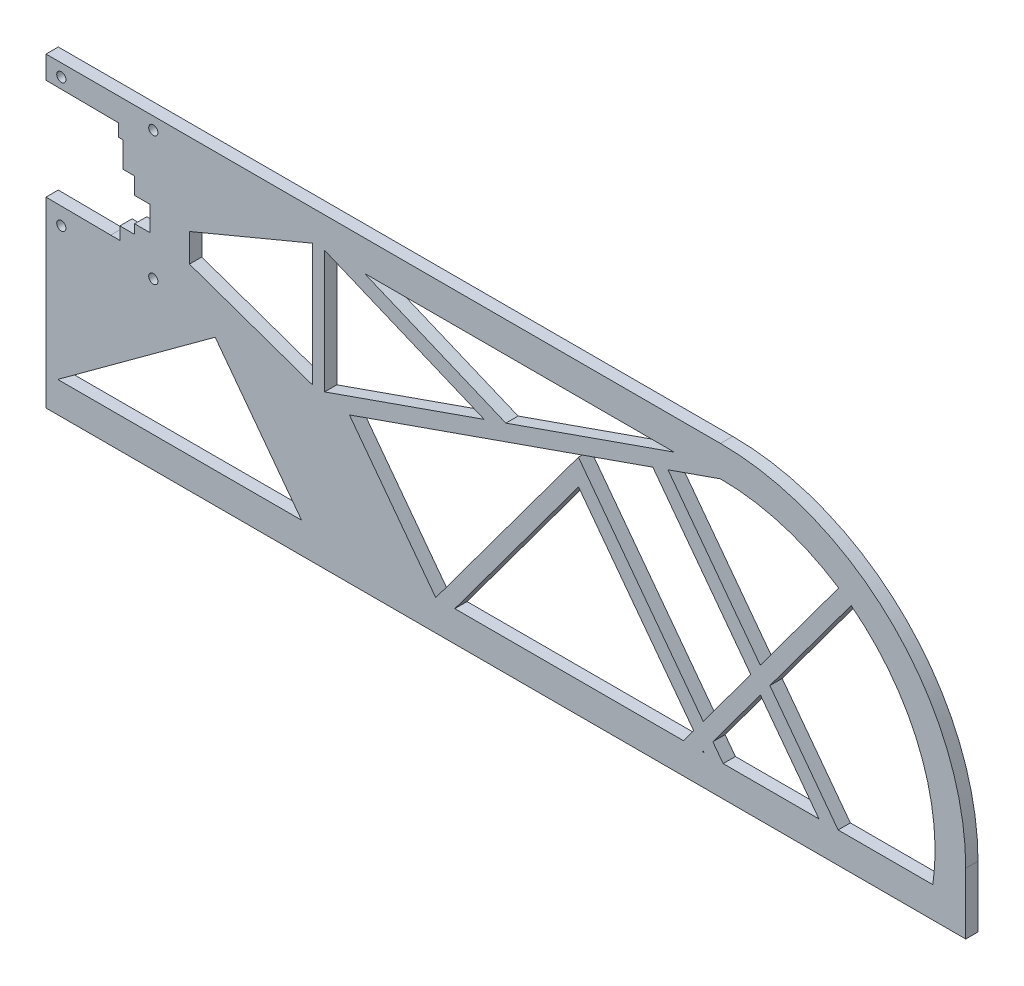
SolidWorks part; units mm, degrees
material "轻木"
ref_plane "前视基准面" through (0, 0, 0) normal (0, 0, 1) x (1, 0, 0)
ref_plane "上视基准面" through (0, 0, 0) normal (0, 1, 0) x (1, 0, 0)
ref_plane "右视基准面" through (0, 0, 0) normal (1, 0, 0) x (0, 0, -1)
other "Configuration Table"
sketch "草图1" plane through (0, 0, 0) normal (0, 0, 1) x (1, 0, 0)
  line L0 (-140, 40) -> (-140, -40)
  line L1 (-150, 50) -> (70, 50)
  line L2 (-150, 50) -> (-150, -50)
  line L3 (-150, -50) -> (150, -50)
  line L4 (150, -30) -> (150, -50)
  line L5 (-150, 50) -> (150, -50) construction
  line L6 (-150, -50) -> (150, 50) construction
  line L7 (-140, -40) -> (140, -40)
  line L8 (140, -30) -> (140, -40)
  line L9 (-140, 40) -> (70, 40)
  arc A0 (70, 50) -> (150, -30) centre (70, -30) cw
  arc A1 (70, 40) -> (140, -30) centre (70, -30) cw
  point P0 (0, 0)
  dimension "D3" = 80
  dimension "D1" = 100
  dimension "D2" = 300
  dimension "D4" = 10
extrude "凸台-拉伸1" add sketch "草图1" along normal blind 4 contours A1 L9 L0 L7 L8 | A0 L1 L2 L3 L4 L9 A1 L8 L7 L0 region at (-6.1257, -1.2001, 0) region at (-40, 46.8377, 0)
sketch "草图4" plane through (0, 0, 4) normal (0, 0, 1) x (1, 0, 0)
  line L0 (-148.2364, 38.3) -> (-148.2364, 13.5)
  line L1 (-148.2364, 13.5) -> (-128.9164, 13.5)
  line L2 (-128.9164, 13.5) -> (-128.9164, 9.4)
  line L3 (-128.9164, 9.4) -> (-125.9104, 9.4)
  line L4 (-125.9104, 9.4) -> (-125.9104, 13.5)
  line L5 (-125.9104, 13.5) -> (-121.1027, 13.5)
  line L6 (-121.1027, 13.5) -> (-121.1027, 16.5)
  line L8 (-116.0966, 16.5) -> (-116.0966, 24.5)
  line L10 (-121.1027, 24.5) -> (-121.1027, 30)
  line L11 (-121.1027, 30) -> (-124.9086, 30)
  line L12 (-124.9086, 30) -> (-124.9086, 38.3)
  line L13 (-124.9086, 38.3) -> (-126.4113, 38.3)
  line L14 (-126.4113, 38.3) -> (-126.4113, 42.4)
  line L15 (-126.4113, 42.4) -> (-128.9164, 42.4)
  line L16 (-128.9164, 42.4) -> (-128.9164, 38.3)
  line L17 (-128.9164, 38.3) -> (-148.2364, 38.3)
  line L18 (-130.2675, 13.5) -> (-142.167, 13.5) construction
  line L19 (-128.9164, 9.4) -> (-150, 9.5917)
  line L20 (-150, 42.5917) -> (-150, 9.5917)
  line L21 (-128.9164, 42.4) -> (-150, 42.5917)
  line L22 (-150, 50) -> (-150, -50) construction
  line L23 (-116.0966, 24.5) -> (-121.1027, 24.5)
  line L24 (-116.0966, 16.5) -> (-121.1027, 16.5)
  dimension "D1" = 8
  dimension "D2" = 3
extrude "切除-拉伸1" cut sketch "草图4" against normal through all contours L16 L17 L0 L1 L2 L3 L4 L5 L6 L24 L8 L10 L11 L12 L13 L14 L15 | L21 L17 L16 | L19 L2 L1 region at (-134.0495, 25.1804, 4) region at (-148.6296, 25.9, 4)
ref_plane "基准面1" through (0, 0, 2) normal (0, 0, 1) x (1, 0, 0)
sketch "草图7" plane through (0, 0, 2) normal (0, 0, 1) x (1, 0, 0)
  line L0 (-145.003, 46) -> (-115.003, 46) construction
  line L1 (-145.003, 46) -> (-145.003, 4) construction
  line L2 (-59.1251, 0) -> (-89.1255, 0)
  line L3 (-150.2532, 0) -> (-111.2531, 0) construction
  line L4 (-100, 0) -> (-140, -29.2842)
  line L5 (-94.8214, -2.4055) -> (-146.1727, -40)
  line L6 (-59.1251, 40) -> (-59.1251, 0)
  line L7 (-89.1255, 0) -> (-59.1255, -40)
  line L8 (-94.8214, -2.4055) -> (-66.6255, -40)
  line L9 (-51.0307, -2.4591) -> (24.4588, 24.0236)
  line L10 (70, 40) -> (-111.1027, 40)
  line L11 (-115.9104, -0.6) -> (-128.9619, -0.6)
  line L12 (-140, -40) -> (140, -40)
  line L13 (140, -40) -> (140, -30)
  line L14 (54.8958, 40) -> (-46.144, 40)
  line L16 (-146.1727, -40) -> (-66.6255, -40)
  line L18 (54.8958, 40) -> (-0.0018, 20.7412)
  line L19 (-59.1251, 40) -> (-7.0548, 18.2669)
  line L20 (-46.144, 40) -> (-0.0018, 20.7412)
  line L21 (-59.1251, 0) -> (-29.1251, -40)
  line L22 (-51.0307, -2.4591) -> (-22.8751, -40)
  line L23 (23.6925, 14.5765) -> (61.2687, -35.5251)
  line L24 (23.1909, 23.5787) -> (64.3713, -31.3285)
  line L25 (47.9314, 32.258) -> (79.8842, -10.3458)
  line L26 (52.8795, 33.9939) -> (82.9868, -6.1492)
  line L27 (24.4588, 24.0236) -> (-22.8751, -40)
  line L28 (23.6925, 14.5765) -> (-16.657, -40)
  line L29 (108.5506, 28.4282) -> (82.9868, -6.1492)
  line L30 (112.6236, 25.5268) -> (86.1182, -10.3244)
  line L31 (-7.0548, 18.2669) -> (-59.1251, 0)
  line L32 (52.8795, 33.9939) -> (70, 40)
  line L33 (23.1909, 23.5787) -> (47.9314, 32.258)
  line L34 (61.2687, -35.5251) -> (57.9603, -40)
  line L35 (64.4001, -39.7002) -> (64.6249, -40)
  line L36 (64.4001, -39.7002) -> (64.1784, -40)
  line L37 (67.5027, -35.5036) -> (70.8749, -40)
  line L38 (79.8842, -10.3458) -> (64.3713, -31.3285)
  line L39 (83.0156, -14.5209) -> (102.1249, -40)
  line L40 (83.0156, -14.5209) -> (67.5027, -35.5036)
  line L41 (-100, 0) -> (-140, 0)
  line L42 (-59.1255, -40) -> (-29.1251, -40)
  line L43 (70.8749, -40) -> (102.1249, -40)
  line L44 (86.1182, -10.3244) -> (108.3749, -40)
  line L45 (-16.657, -40) -> (57.9603, -40)
  line L46 (64.1784, -40) -> (64.6249, -40)
  line L47 (-61.1251, 38.1251) -> (-61.1251, 14.6296) construction
  line L48 (-115.1953, 18.2669) -> (-63.1251, 0)
  line L49 (-63.1251, 40) -> (-63.1251, 0)
  line L50 (-63.1251, 40) -> (-115.1953, 18.2669)
  line L51 (108.3749, -40) -> (139.282, -40)
  line L61 (-103.1953, 23.2755) -> (-103.1953, 14.0572)
  line L83 (-115.9104, -0.6) -> (-128.9619, -0.6)
  line L84 (-128.9619, -0.6) -> (-140, -0.4997)
  line L85 (-128.9619, -0.6) -> (-140, -0.4997)
  line L86 (-140, -0.4997) -> (-140, -40)
  line L87 (-140, -0.4997) -> (-140, -40)
  line L88 (-111.1027, 40) -> (-111.1027, 34.5)
  line L89 (-111.1027, 40) -> (-111.1027, 34.5)
  line L90 (-111.1027, 34.5) -> (-106.0966, 34.5)
  line L91 (-111.1027, 34.5) -> (-106.0966, 34.5)
  line L92 (-106.0966, 34.5) -> (-106.0966, 6.5)
  line L93 (-106.0966, 34.5) -> (-106.0966, 6.5)
  line L94 (-106.0966, 6.5) -> (-111.1027, 6.5)
  line L95 (-106.0966, 6.5) -> (-111.1027, 6.5)
  line L96 (-111.1027, 6.5) -> (-111.1027, 3.5)
  line L97 (-111.1027, 6.5) -> (-111.1027, 3.5)
  line L98 (-111.1027, 3.5) -> (-115.9104, 3.5)
  line L99 (-111.1027, 3.5) -> (-115.9104, 3.5)
  line L100 (-115.9104, 3.5) -> (-115.9104, -0.6)
  line L101 (-115.9104, 3.5) -> (-115.9104, -0.6)
  circle A0 centre (-145.003, 46) radius 1.5
  circle A4 centre (-115.003, 46) radius 1.5
  circle A5 centre (-115.003, 4) radius 1.5
  circle A6 centre (-145.003, 4) radius 1.5
  arc A7 (108.5506, 28.4282) -> (70, 40) centre (70, -30) ccw
  arc A9 (140, -30) -> (70, 40) centre (70, -30) ccw
  arc A10 (139.282, -40) -> (112.6236, 25.5268) centre (70, -30) ccw
  dimension "D1" = 3
  dimension "D2" = 90
  dimension "D3" = 30
  dimension "D4" = 42
  dimension "D6" = 5
  dimension "D7" = 50
  dimension "D8" = 5
  dimension "D9" = 5
  dimension "D10" = 50
  dimension "D11" = 5
  dimension "D12" = 5
  dimension "D13" = 5
  dimension "D14" = 25
  dimension "D15" = 70
  dimension "D16" = 5
  dimension "D17" = 5
  dimension "D18" = 60
  dimension "D21" = 5
  dimension "D22" = 6
  dimension "D23" = 40
  dimension "D24" = 36.208
  dimension "D25" = 80
  dimension "D26" = 30.0004
  dimension "D27" = 2
  dimension "D28" = 12
  dimension "D5" = 10
  dimension "D19" = 2
  dimension "D20" = 2
extrude "切除-拉伸2" cut sketch "草图7" against normal through all and the other way through all contours L37 L43 L39 L40 | L44 A10 L30 | L36 L46 L35 | L28 L45 L34 L23 | L38 L25 L33 L24 | L29 A7 L32 L26 | L49 L50 L48 | L16 L8 L5 | L14 L20 L18 | L6 L31 L19 | L9 L27 L22 | A0 | A6 | A5 | A4 region at (-78.9835, 19.4722, 2) region at (23.6337, -21.6948, 2) region at (53.431, 3.222, 2) region at (81.2604, 22.2408, 2) region at (64.4011, -39.9001, 2) region at (115.8053, -12.1866, 2) region at (83.6074, -31.2821, 2)
